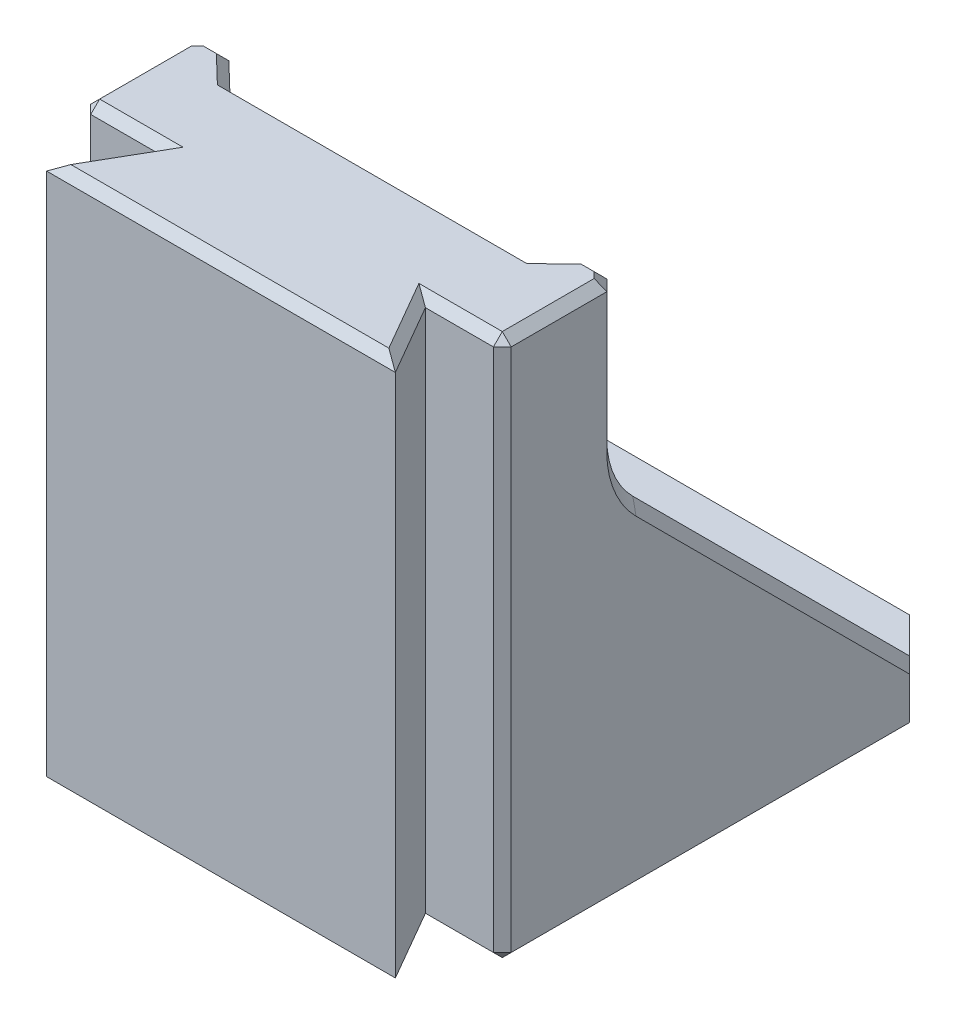
SolidWorks part; units mm, degrees
material "ABS"
ref_plane "Front Plane" through (0, 0, 0) normal (0, 0, 1) x (1, 0, 0)
ref_plane "Top Plane" through (0, 0, 0) normal (0, 1, 0) x (1, 0, 0)
ref_plane "Right Plane" through (0, 0, 0) normal (1, 0, 0) x (0, 0, -1)
sketch "Sketch1" plane through (0, 0, 0) normal (0, 1, 0) x (1, 0, 0)
  line L0 (-21.15, 17.15) -> (-17.15, 21.15)
  line L1 (-17, -21.15) -> (17, -21.15)
  line L2 (-21.15, -17.15) -> (-21.15, 17.15)
  line L3 (-17.15, 21.15) -> (17.15, 21.15)
  line L4 (21.15, -17.15) -> (21.15, 17.15)
  line L5 (-21.15, -21.15) -> (21.15, 21.15) construction
  line L6 (-21.15, 21.15) -> (21.15, -21.15) construction
  line L7 (-21.15, -17.15) -> (-17, -21.15)
  line L8 (17, -21.15) -> (21.15, -17.15)
  line L9 (17.15, 21.15) -> (21.15, 17.15)
  circle A0 centre (-15.5, 15.5) radius 1.5
  circle A1 centre (15.5, 15.5) radius 1.5
  circle A2 centre (15.5, -15.5) radius 1.5
  circle A3 centre (-15.5, -15.5) radius 1.5
  circle A4 centre (0, 0) radius 11.5
  point P0 (0, 0)
  point P22 (0, -21.15)
  dimension "D3" = 3
  dimension "D4" = 3
  dimension "D9" = 3
  dimension "D10" = 3
  dimension "D12" = 23
  dimension "D1" = 42.3
  dimension "D2" = 42.3
  dimension "D13" = 34
  dimension "D11" = 31
  dimension "D6" = 4
  dimension "D7" = 4
extrude "Bracket Face Extrude" add sketch "Sketch1" along normal blind 5
sketch "Sketch5" plane through (0, 0, 0) normal (0, 1, 0) x (1, 0, 0)
  line L0 (-23.65, -18.2126) -> (-23.65, -31.15)
  line L1 (-23.65, -31.15) -> (23.65, -31.15)
  line L2 (23.65, -31.15) -> (23.65, -18.2126)
  line L16 (-23.65, 18.1855) -> (-23.65, -18.2126)
  line L17 (-23.65, -18.2126) -> (-18.0087, -23.65)
  line L18 (-18.0087, -23.65) -> (18.0087, -23.65)
  line L19 (18.0087, -23.65) -> (23.65, -18.2126)
  line L20 (23.65, -18.2126) -> (23.65, 18.1855)
  line L21 (23.65, 18.1855) -> (18.1855, 23.65)
  line L22 (18.1855, 23.65) -> (-18.1855, 23.65)
  line L23 (-18.1855, 23.65) -> (-23.65, 18.1855)
  line L24 (-23.65, 14.65) -> (-23.65, -18.2126)
  line L25 (-23.65, -18.2126) -> (-18.0087, -23.65) construction
  line L26 (-18.0087, -23.65) -> (18.0087, -23.65) construction
  line L27 (18.0087, -23.65) -> (23.65, -18.2126) construction
  line L28 (23.65, -18.2126) -> (23.65, 14.65)
  line L29 (23.65, 18.1855) -> (18.1855, 23.65) construction
  line L30 (18.1855, 23.65) -> (-18.1855, 23.65) construction
  line L31 (-18.1855, 23.65) -> (-23.65, 18.1855) construction
  line L32 (-21.15, 17.15) -> (-23.65, 14.65)
  line L33 (21.15, 17.15) -> (23.65, 14.65)
  line L34 (-23.65, 18.1855) -> (-23.65, 14.65) construction
  line L35 (23.65, 14.65) -> (23.65, 18.1855) construction
  line L40 (-21.15, 17.15) -> (-21.15, -17.15)
  line L41 (-21.15, -17.15) -> (-17, -21.15)
  line L42 (-17, -21.15) -> (17, -21.15)
  line L43 (17, -21.15) -> (21.15, -17.15)
  line L44 (21.15, -17.15) -> (21.15, 17.15)
  line L45 (21.15, 17.15) -> (17.15, 21.15)
  line L46 (17.15, 21.15) -> (-17.15, 21.15)
  line L47 (-17.15, 21.15) -> (-21.15, 17.15)
  line L48 (-21.15, 17.15) -> (-21.15, -17.15)
  line L49 (-21.15, -17.15) -> (-17, -21.15)
  line L50 (-17, -21.15) -> (17, -21.15)
  line L51 (17, -21.15) -> (21.15, -17.15)
  line L52 (21.15, -17.15) -> (21.15, 17.15)
  line L53 (21.15, 17.15) -> (17.15, 21.15) construction
  line L54 (17.15, 21.15) -> (-17.15, 21.15) construction
  line L55 (-17.15, 21.15) -> (-21.15, 17.15) construction
  dimension "D3" = 10
  dimension "D1" = 2.5
  dimension "D2" = 0
extrude "Bracket Body Extrude" add sketch "Sketch5" along normal blind 61
sketch "Sketch6" plane through (0, 0, 0) normal (1, 0, 0) x (0, 0, -1)
  line L0 (17.15, 5) -> (-15.2211, 37.3711)
  line L1 (-18.15, 44.4421) -> (-18.15, 61)
  line L3 (-18.15, 61) -> (17.15, 61)
  line L4 (17.15, 61) -> (17.15, 5)
  line L6 (-31.15, 61) -> (-31.15, 0) construction
  line L7 (-31.15, 61) -> (14.65, 61) construction
  arc A0 (-15.2211, 37.3711) -> (-18.15, 44.4421) centre (-8.15, 44.4421) cw
  dimension "D3" = 10
  dimension "D1" = 13
  dimension "D2" = 45
extrude "Bracket Side Trim" cut sketch "Sketch6" against normal through all both and the other way through all
chamfer "Bracket Side Edge Chamfer" distance 1.25 angle 45 6 edges at (-23.65, 52.7211, 18.15) (-23.65, 22.4355, 0.2855) (23.65, 52.7211, 18.15) (23.65, 22.4355, 0.2855) (-23.65, 40.6153, 17.3888) (23.65, 40.6153, 17.3888)
chamfer "Bracket Mount Hole Chamfer" distance 0.75 angle 45 4 edges at (-15.5, 0, 17) (-15.5, 0, -14) (15.5, 0, 17) (15.5, 0, -14)
sketch "Sketch9" plane through (0, 0, 0) normal (0, 1, 0) x (1, 0, 0)
  line L0 (-15, -31.15) -> (-19.6188, -39.15)
  line L1 (-19.6188, -39.15) -> (19.6188, -39.15)
  line L2 (19.6188, -39.15) -> (15, -31.15)
  line L3 (15, -31.15) -> (-15, -31.15)
  line L4 (-23.65, -31.15) -> (23.65, -31.15) construction
  point P8 (0, -39.15)
  dimension "D1" = 60
  dimension "D3" = 8
  dimension "D4" = 30
extrude "Slide Tab Extrude" add sketch "Sketch9" along normal up to surface (61 mm away) up to face at (0, 61, 21.6)
chamfer "Bracket Face Chamfer" distance 1 angle 45 26 edges at (17.3094, 0, 35.15) (-17.3094, 0, 35.15) (-23.65, 0, 8.25) (23.65, 0, 8.25) (20.4, 0, -17.9) (-20.4, 0, -17.9) (0, 0, -21.15) (17.3094, 61, 35.15) (0, 61, 39.15) (-17.3094, 61, 35.15) (0, 0, 39.15) (-18.5562, 61, 19.65) (0, 61, 21.15) (18.5562, 61, 19.65) (21.2562, 61, 18.15) (23.025, 61, 18.775) (23.65, 61, 25.275) (19.325, 61, 31.15) (-19.325, 61, 31.15) (-21.2562, 61, 18.15) (-23.025, 61, 18.775) (-23.65, 61, 25.275) (23.65, 30.5, 31.15) (-23.65, 30.5, 31.15) (-19.325, 0, 31.15) (19.325, 0, 31.15)
sketch "Sketch15" [suppressed] plane through (0, 0, 0) normal (0, -1, 0) x (-1, 0, 0)
  circle A4 centre (0, 0) radius 13.6
  circle A5 centre (0, 0) radius 11.5 construction
  circle A6 centre (0, 0) radius 11.5 construction
  dimension "D4" = 27.2
extrude "Rotary Potentiometer Mount" [suppressed] add sketch "Sketch15" along normal blind 4
sketch "Sketch16" [suppressed] plane through (0, -4, 0) normal (0, -1, 0) x (1, 0, 0)
  circle A2 centre (0, 0) radius 6
  dimension "D4" = 12
extrude "Rotary Potentiometer Mounting Holes" [suppressed] cut sketch "Sketch16" against normal through all
chamfer "Pot Mount Main Chamfer" [suppressed] distance 4 angle 45
chamfer "Main Through Hole Chamfers" [suppressed] distance 1 angle 45
